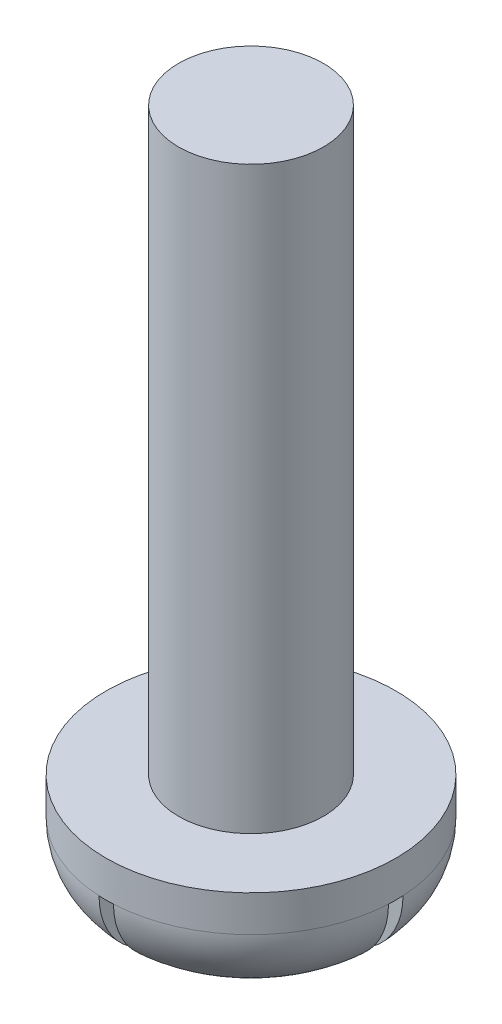
SolidWorks part; units mm, degrees
ref_plane "前视基准面" through (0, 0, 0) normal (0, 0, 1) x (1, 0, 0)
ref_plane "上视基准面" through (0, 0, 0) normal (0, 1, 0) x (1, 0, 0)
ref_plane "右视基准面" through (0, 0, 0) normal (1, 0, 0) x (0, 0, -1)
other "Configuration Table"
sketch "草图1" plane through (0, 0, 0) normal (0, 1, 0) x (1, 0, 0)
  circle A0 centre (0, 0) radius 2
  dimension "D1" = 4
extrude "凸台-拉伸1" add sketch "草图1" against normal blind 1.5
sketch "草图2" plane through (0, 0, 0) normal (0, 1, 0) x (1, 0, 0)
  circle A0 centre (0, 0) radius 1
  dimension "D1" = 2
extrude "凸台-拉伸2" add sketch "草图2" along normal blind 8 contours A0
sketch "草图4" plane through (0, -1.5, 0) normal (0, -1, 0) x (1, 0, 0)
  line L0 (-2, 0) -> (2, 0)
  line L1 (0, 2) -> (0, -2)
  circle A1 centre (0, 0) radius 2 construction
extrude "切除-拉伸-薄壁1" cut sketch "草图4" against normal blind 1 and the other way through all thin thin type mid plane wall 0.2
ref_axis "基准轴1" through (0, 19.8772, 0) along (0, -1, 0)
fillet "圆角1" radius 1 4 edges at (1.4142, -1.5, 1.4142) (-1.4142, -1.5, 1.4142) (-1.4142, -1.5, -1.4142) (1.4142, -1.5, -1.4142)
